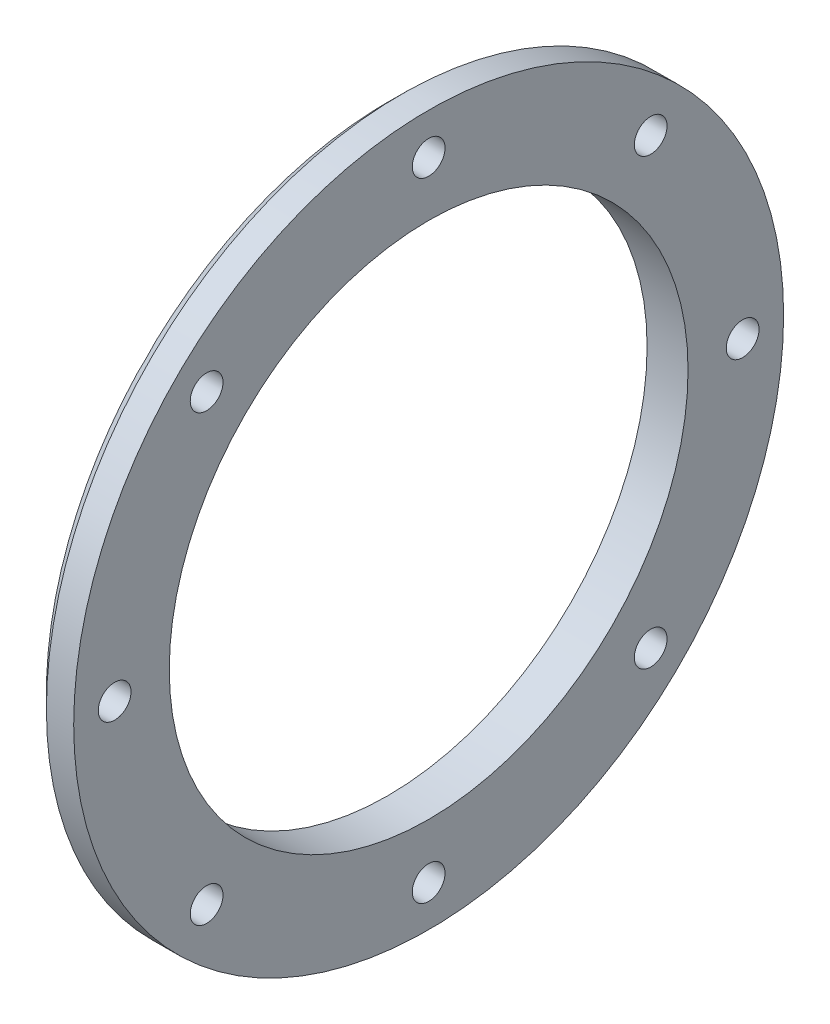
SolidWorks part; units mm, degrees
material "ABS"
ref_plane "Спереди" through (0, 0, 0) normal (0, 0, 1) x (1, 0, 0)
ref_plane "Сверху" through (0, 0, 0) normal (0, 1, 0) x (1, 0, 0)
ref_plane "Справа" through (0, 0, 0) normal (1, 0, 0) x (0, 0, -1)
sketch "Эскиз1" plane through (0, 0, 0) normal (0, 0, 1) x (1, 0, 0)
  line L5 (0, 19) -> (0, 25)
  line L6 (0, 25) -> (1, 26)
  line L7 (1, 26) -> (3, 26)
  line L8 (3, 26) -> (3, 19)
  line L9 (3, 19) -> (0, 19)
  line L10 (0, 0) -> (0, 19) construction
  line L11 (0, 0) -> (16163.9124, 0) construction
  point P7 (1.5, 19)
  dimension "D1" = 52
  dimension "D2" = 3
  dimension "D3" = 1
  dimension "D4" = 45
  dimension "D5" = 38
revolve "Повернуть1" add sketch "Эскиз1" angle 360 about L11
hole_wizard "Зенковка для винта с потайной головкой M21" positions "Эскиз2" profile "Эскиз3" countersink size "M2" standard "HASCO Metric" end condition through all
sketch "Эскиз2" plane through (0, 0, 0) normal (-1, 0, 0) x (0, 0, 1)
  line L0 (0, 0) -> (23, 0) construction
  line L2 (0, 0) -> (16.2635, 16.2635) construction
  circle A0 centre (0, 0) radius 23 construction
  point P0 (16.2635, 16.2635)
  dimension "D1" = 46
  dimension "D2" = 45
sketch "Эскиз3" plane through (0, 16.2635, 16.2635) normal (0, 1, 0) x (0, 0, 1)
  line L0 (0, 0) -> (0, 3)
  line L1 (0, 3) -> (1.2, 3)
  line L2 (1.2, 3) -> (1.2, 1)
  line L3 (1.2, 1) -> (2.2, 0)
  line L5 (2.2, 0) -> (0, 0)
  line L6 (-1.2, 1) -> (-2.2, 0) construction
  line L11 (0, -6.35) -> (0, 107.95) construction
  dimension "Диаметр сквозного отверстия" = 2.4
  dimension "Глубина сквозного отверстия" = 3
  dimension "Диаметр передней зенковки" = 4.4
  dimension "Угол передней зенковки" = 90
pattern_circular "Круговой массив1" count 8 over 360 about axis through (1, 0, 0) along (-1, 0, 0) of "Зенковка для винта с потайной головкой M21"
